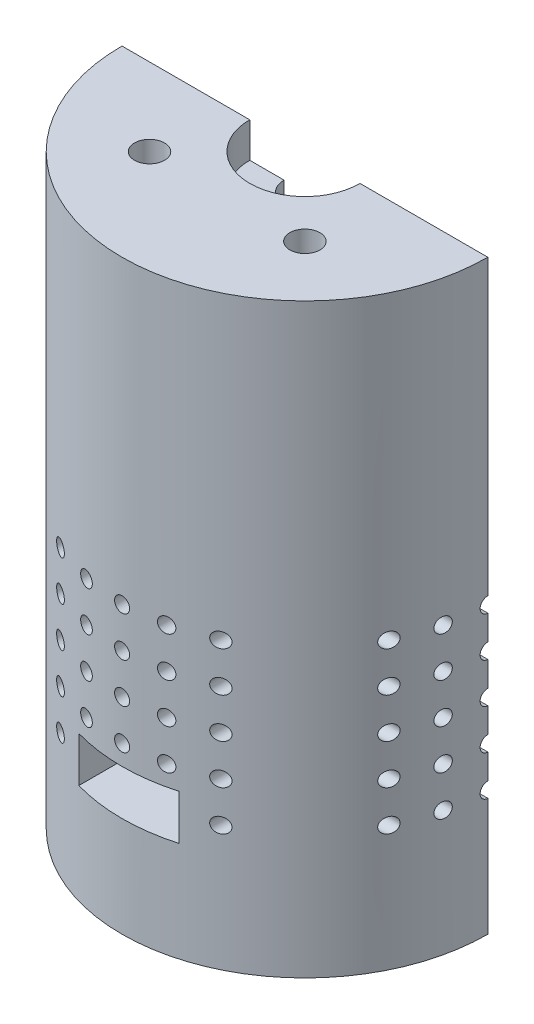
SolidWorks part; units mm, degrees
ref_plane "Front Plane" through (0, 0, 0) normal (0, 0, 1) x (1, 0, 0)
ref_plane "Top Plane" through (0, 0, 0) normal (0, 1, 0) x (1, 0, 0)
ref_plane "Right Plane" through (0, 0, 0) normal (1, 0, 0) x (0, 0, -1)
sketch "Sketch1" plane through (0, 0, 0) normal (0, 1, 0) x (1, 0, 0)
  line L1 (-75, -75) -> (75, -75)
  line L2 (-75, -75) -> (-75, 75)
  line L3 (-75, 75) -> (75, 75)
  line L4 (75, -75) -> (75, 75)
  line L5 (-75, -75) -> (75, 75) construction
  line L6 (-75, 75) -> (75, -75) construction
  point P0 (0, 0)
  dimension "D1" = 150
  dimension "D2" = 150
extrude "Boss-Extrude1" add sketch "Sketch1" along normal blind 20
sketch "Sketch2" plane through (0, 20, 0) normal (0, 1, 0) x (1, 0, 0)
  line L1 (-21.15, -21.15) -> (21.15, -21.15)
  line L2 (-21.15, -21.15) -> (-21.15, 21.15)
  line L3 (-21.15, 21.15) -> (21.15, 21.15)
  line L4 (21.15, -21.15) -> (21.15, 21.15)
  line L5 (-21.15, -21.15) -> (21.15, 21.15) construction
  line L6 (-21.15, 21.15) -> (21.15, -21.15) construction
  line L11 (-24.15, -24.15) -> (21.15, 21.15) construction
  line L12 (-21.15, 21.15) -> (21.15, -21.15) construction
  circle A0 centre (0, 0) radius 36.5
  point P0 (0, 0)
  point P6 (0, 0)
  dimension "D3" = 73
  dimension "D1" = 42.3
  dimension "D2" = 42.3
extrude "Boss-Extrude2" add sketch "Sketch2" along normal blind 50
sketch "Sketch3" plane through (0, 0, -21.15) normal (0, 0, 1) x (1, 0, 0)
  line L0 (21.15, 20) -> (-21.15, 20) construction
  line L1 (-5, 20) -> (5, 20)
  line L2 (-5, 20) -> (-5, 29)
  line L3 (-5, 29) -> (5, 29)
  line L4 (5, 20) -> (5, 29)
  line L5 (-5, 29) -> (5, 20) construction
  line L6 (-5, 20) -> (5, 29) construction
  line L7 (-21.15, 70) -> (-21.15, 20) construction
  point P6 (0, 24.5)
  dimension "D1" = 21.15
  dimension "D2" = 10
  dimension "D3" = 9
extrude "Cut-Extrude1" cut sketch "Sketch3" against normal up to next
sketch "Sketch4" plane through (0, 0, 21.15) normal (0, 0, -1) x (-1, 0, 0)
  line L0 (21.15, 20) -> (-21.15, 20) construction
  line L2 (21.15, 70) -> (21.15, 20) construction
  circle A0 centre (0, 25) radius 1.5
  circle A1 centre (16, 25) radius 1.5
  circle A2 centre (-16, 25) radius 1.5
  circle A3 centre (-8, 25) radius 1.5
  circle A4 centre (8, 25) radius 1.5
  dimension "D1" = 3
  dimension "D2" = 5
  dimension "D3" = 5
  dimension "D4" = 5
  dimension "D5" = 5
  dimension "D6" = 5
  dimension "D7" = 8
  dimension "D8" = 8
  dimension "D9" = 8
  dimension "D10" = 8
  dimension "D11" = 21.15
extrude "Cut-Extrude2" cut sketch "Sketch4" against normal up to next
pattern_linear "LPattern1" count 5 spacing 8 along (0, 1, 0) of "Cut-Extrude2"
pattern_circular "CirPattern4" count 4 every 90 about axis through (0, 70, 0) along (0, -1, 0) of "LPattern1", "Cut-Extrude2"
sketch "Sketch10" plane through (0, 70, 0) normal (0, 1, 0) x (1, 0, 0)
  circle A0 centre (0, 0) radius 36.5
  circle A1 centre (0, 0) radius 12
  dimension "D1" = 73
  dimension "D2" = 24
extrude "Boss-Extrude3" add sketch "Sketch10" along normal blind 35
sketch "Sketch11" plane through (0, 105, 0) normal (0, 1, 0) x (1, 0, 0)
  circle A0 centre (0, 0) radius 36.5
  circle A1 centre (0, 0) radius 4.15
  dimension "D1" = 8.3
  dimension "D2" = 73
extrude "Boss-Extrude4" add sketch "Sketch11" along normal blind 5
sketch "Sketch12" plane through (0, 110, 0) normal (0, 1, 0) x (1, 0, 0)
  circle A0 centre (0, 0) radius 36.5
  circle A1 centre (0, 0) radius 11
  dimension "D1" = 22
  dimension "D2" = 73
extrude "Boss-Extrude5" add sketch "Sketch12" along normal blind 7
sketch "Sketch7" plane through (0, 0, -75) normal (0, 0, -1) x (-1, 0, 0)
  line L1 (-75, 0) -> (75, 0)
  line L2 (-75, 0) -> (-75, 2000)
  line L3 (-75, 2000) -> (75, 2000)
  line L4 (75, 0) -> (75, 2000)
  dimension "D1" = 2000
extrude "Cut-Extrude4" cut sketch "Sketch7" against normal blind 75
sketch "Sketch13" plane through (0, 117, 0) normal (0, 1, 0) x (1, 0, 0)
  line L0 (-36.5, 0) -> (-11, 0) construction
  line L1 (11, 0) -> (36.5, 0) construction
  circle A0 centre (15.5, -15.5) radius 3
  circle A1 centre (-15.5, -15.5) radius 3
  arc A5 (-11, 0) -> (11, 0) centre (0, 0) ccw construction
  dimension "D1" = 6
  dimension "D2" = 6
  dimension "D6" = 15.5
  dimension "D3" = 15.5
  dimension "D4" = 15.5
  dimension "D5" = 31
extrude "Cut-Extrude5" cut sketch "Sketch13" against normal blind 40
sketch "Sketch14" plane through (0, 77, 0) normal (0, 1, 0) x (1, 0, 0)
  circle A0 centre (-15.5, -15.5) radius 1.5
  circle A1 centre (15.5, -15.5) radius 1.5
  dimension "D1" = 3
  dimension "D2" = 3
extrude "Cut-Extrude6" cut sketch "Sketch14" against normal up to next
sketch "Sketch15" plane through (0, 0, 21.15) normal (0, 0, -1) x (-1, 0, 0)
  line L0 (21.15, 20) -> (-21.15, 20) construction
  line L1 (-10, 20) -> (10, 20)
  line L2 (-10, 20) -> (-10, 29)
  line L3 (-10, 29) -> (10, 29)
  line L4 (10, 20) -> (10, 29)
  line L5 (21.15, 70) -> (21.15, 20) construction
  dimension "D1" = 9
  dimension "D2" = 20
  dimension "D3" = 11.15
extrude "Cut-Extrude7" cut sketch "Sketch15" against normal up to next
sketch "Sketch16" plane through (0, 20, 0) normal (0, 1, 0) x (1, 0, 0)
  line L0 (21.15, 0) -> (-21.15, 0) construction
  circle A0 centre (0, 0) radius 36.5
  circle A1 centre (0, 0) radius 117.6995
  dimension "D1" = 73
extrude "Cut-Extrude8" cut sketch "Sketch16" against normal up to next
